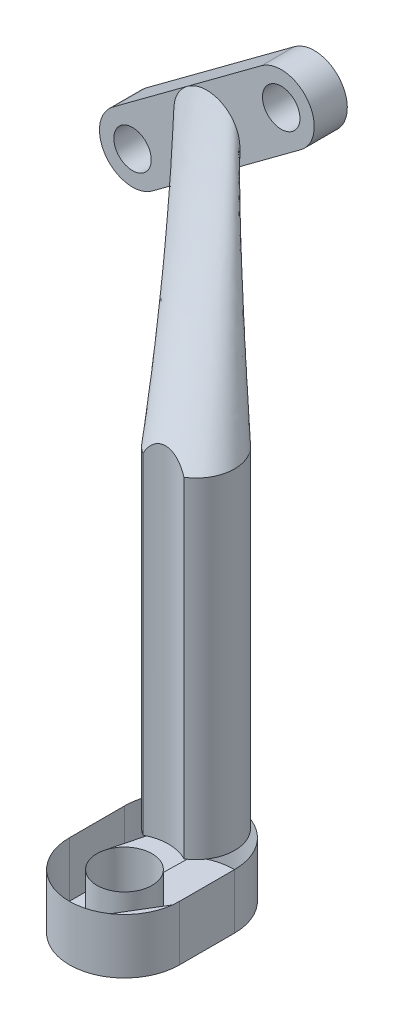
SolidWorks part; units mm, degrees
ref_plane "Ebene vorne" through (0, 0, 0) normal (0, 0, 1) x (1, 0, 0)
ref_plane "Ebene oben" through (0, 0, 0) normal (0, 1, 0) x (1, 0, 0)
ref_plane "Ebene rechts" through (0, 0, 0) normal (1, 0, 0) x (0, 0, -1)
sketch "Skizze1" plane through (0, 0, 0) normal (0, 1, 0) x (1, 0, 0)
  line L0 (0, 0) -> (0, 5) construction
  line L1 (-5, 0) -> (-5, 5)
  line L2 (5, 0) -> (5, 5)
  arc A1 (-5, 0) -> (5, 0) centre (0, 0) ccw
  arc A2 (5, 5) -> (-5, 5) centre (0, 5) ccw
  point P4 (0, 2.5)
  dimension "D2" = 10
  dimension "D3" = 5
extrude "Aufsatz-Linear austragen1" add sketch "Skizze1" along normal blind 5
ref_plane "Ebene1" through (0, 0, -16.1) normal (0, 0, 1) x (1, 0, 0)
sketch "Skizze3" plane through (0, 0, -16.1) normal (0, 0, 1) x (1, 0, 0)
  circle A0 centre (-8.62, 50.91) radius 3
  point P0 (-8.62, 50.91)
  dimension "D2" = 6
  dimension "D1" = 8.62
  dimension "D4" = 50.91
sketch "Skizze4" plane through (0, 5, 0) normal (0, 1, 0) x (1, 0, 0)
  circle A0 centre (0, 0) radius 2.5
  dimension "D1" = 5
extrude "Schnitt-Linear austragen1" cut sketch "Skizze4" against normal blind 10
sketch "Skizze5" plane through (0, 5, 0) normal (0, 1, 0) x (1, 0, 0)
  line L0 (0, 0) -> (0, 6.5) construction
  circle A0 centre (0, 6.5) radius 3.5
  arc A1 (5, 5) -> (-5, 5) centre (0, 5) ccw construction
  dimension "D1" = 7
extrude "Aufsatz-Linear austragen2" add sketch "Skizze5" along normal blind 30
sketch "Skizze6" plane through (0, 35, 0) normal (0, 1, 0) x (1, 0, 0)
  circle A0 centre (0, 6.5) radius 3.5
loft "Ausformung4" add profiles "Skizze6", "Skizze3" connector at (0, 35, -3) connector at (-11.6186, 51.0029, -16.1)
sketch "Skizze7" plane through (0, 5, 0) normal (0, 1, 0) x (1, 0, 0)
  circle A0 centre (0, 0) radius 4
  dimension "D1" = 8
extrude "Schnitt-Linear austragen2" cut sketch "Skizze7" along normal blind 40
sketch "Skizze8" plane through (0, 0, -16.1) normal (0, 0, 1) x (1, 0, 0)
  line L0 (-1.8702, 55.91) -> (-15.3698, 45.91) construction
  line L1 (-0.0845, 53.4994) -> (-13.584, 43.4993)
  line L2 (-3.656, 58.3207) -> (-17.1555, 48.3206)
  line L3 (-8.62, 50.91) -> (2.4662, 50.91) construction
  arc A0 (-0.0845, 53.4994) -> (-3.656, 58.3207) centre (-1.8702, 55.91) ccw
  arc A1 (-17.1555, 48.3206) -> (-13.584, 43.4993) centre (-15.3698, 45.91) ccw
  circle A3 centre (-8.62, 50.91) radius 3 construction
  circle A4 centre (-1.8702, 55.91) radius 1.7
  circle A5 centre (-15.3698, 45.91) radius 1.7
  point P2 (-8.62, 50.91)
  dimension "D4" = 3.4
  dimension "D5" = 3.4
  dimension "D1" = 16.8
  dimension "D2" = 6
  dimension "D3" = 36.53
extrude "Aufsatz-Linear austragen3" add sketch "Skizze8" against normal blind 3
